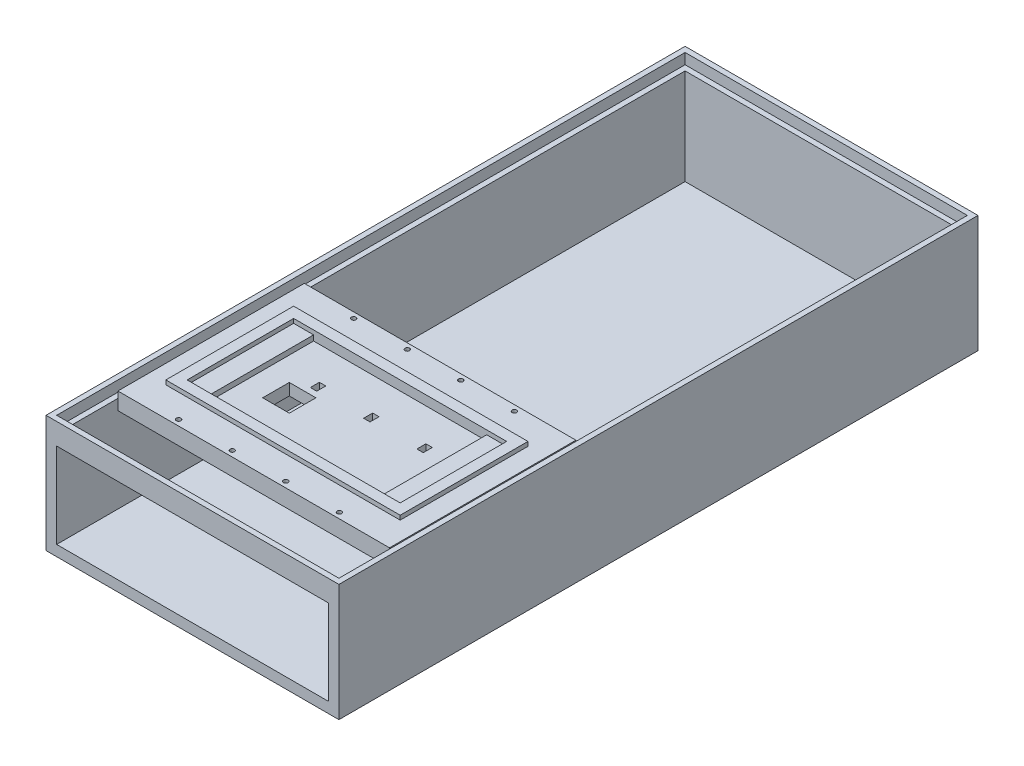
SolidWorks part; units mm, degrees
ref_plane "Front Plane" through (0, 0, 0) normal (0, 0, 1) x (1, 0, 0)
ref_plane "Top Plane" through (0, 0, 0) normal (0, 1, 0) x (1, 0, 0)
ref_plane "Right Plane" through (0, 0, 0) normal (1, 0, 0) x (0, 0, -1)
sketch "Sketch1" plane through (0, 0, 0) normal (0, 1, 0) x (1, 0, 0)
  line L1 (0, 0) -> (139.7, 0)
  line L2 (0, 0) -> (0, 304.8)
  line L3 (0, 304.8) -> (139.7, 304.8)
  line L4 (139.7, 0) -> (139.7, 304.8)
  dimension "D1" = 304.8
  dimension "D2" = 139.7
extrude "Boss-Extrude1" add sketch "Sketch1" along normal blind 5.08
sketch "Sketch2" plane through (0, 5.08, 0) normal (0, 1, 0) x (1, 0, 0)
  line L1 (0, 304.8) -> (139.7, 304.8)
  line L2 (0, 304.8) -> (0, 0)
  line L3 (0, 0) -> (139.7, 0)
  line L4 (139.7, 304.8) -> (139.7, 0)
  line L5 (5.08, 299.72) -> (134.62, 299.72)
  line L6 (5.08, 299.72) -> (5.08, 5.08)
  line L7 (5.08, 5.08) -> (134.62, 5.08)
  line L8 (134.62, 299.72) -> (134.62, 5.08)
  line M9 (0, 304.8) -> (0, 0)
  line M10 (0, 0) -> (139.7, 0)
  line M11 (139.7, 0) -> (139.7, 304.8)
  line M12 (139.7, 304.8) -> (0, 304.8)
  dimension "D1" = 5.08
  dimension "D2" = 5.08
  dimension "D3" = 5.08
  dimension "D4" = 5.08
extrude "Walls" add sketch "Sketch2" along normal blind 50.8 contours L5 L8 L7 L6 M12 M9 M10 M11 region at (69.85, 5.08, -301.4471)
sketch "Sketch3" plane through (0, 55.88, 0) normal (0, 1, 0) x (1, 0, 0)
  line L1 (5.08, 299.72) -> (134.62, 299.72)
  line L2 (5.08, 299.72) -> (5.08, 5.08)
  line L3 (5.08, 5.08) -> (134.62, 5.08)
  line L4 (134.62, 299.72) -> (134.62, 5.08)
  line L5 (2.54, 302.26) -> (137.16, 302.26)
  line L6 (2.54, 302.26) -> (2.54, 2.54)
  line L7 (2.54, 2.54) -> (137.16, 2.54)
  line L8 (137.16, 302.26) -> (137.16, 2.54)
  line M13 (5.08, 299.72) -> (134.62, 299.72)
  line M14 (134.62, 299.72) -> (134.62, 5.08)
  line M15 (134.62, 5.08) -> (5.08, 5.08)
  line M16 (5.08, 5.08) -> (5.08, 299.72)
  dimension "D1" = 2.54
  dimension "D2" = 2.54
  dimension "D3" = 2.54
  dimension "D4" = 2.54
extrude "Cut-Extrude1" cut sketch "Sketch3" against normal blind 5.08 contours L8 L5 L6 L7 M16 M13 M14 M15 region at (69.85, 55.88, -301.9314)
sketch "Sketch5" plane through (0, 5.08, 0) normal (0, 1, 0) x (1, 0, 0)
  line L0 (5.08, 5.08) -> (5.08, 299.72) construction
  line L1 (5.08, 118.11) -> (134.62, 118.11)
  line L2 (5.08, 118.11) -> (5.08, 29.21)
  line L3 (5.08, 29.21) -> (134.62, 29.21)
  line L4 (134.62, 118.11) -> (134.62, 29.21)
  line L6 (134.62, 299.72) -> (134.62, 5.08) construction
  point P8 (134.62, 73.66)
  dimension "D1" = 73.66
  dimension "D2" = 88.9
extrude "Button Support" add sketch "Sketch5" along normal blind 48.768
ref_plane "Plane1" through (0, 0, -73.66) normal (0, 0, 1) x (1, 0, 0)
sketch "Sketch6" plane through (0, 53.848, 0) normal (0, 1, 0) x (1, 0, 0)
  line L0 (0, 0) -> (139.7, 0) construction
  line L1 (19.05, 99.06) -> (120.65, 99.06)
  line L2 (19.05, 99.06) -> (19.05, 48.26)
  line L3 (19.05, 48.26) -> (120.65, 48.26)
  line L4 (120.65, 99.06) -> (120.65, 48.26)
  line L5 (125.73, 104.14) -> (13.97, 104.14)
  line L6 (125.73, 104.14) -> (125.73, 43.18)
  line L7 (125.73, 43.18) -> (13.97, 43.18)
  line L8 (13.97, 104.14) -> (13.97, 43.18)
  line L9 (134.62, 118.11) -> (5.08, 118.11) construction
  point P8 (69.85, 104.14)
  point P9 (69.85, 99.06)
  point P10 (120.65, 73.66)
  point P11 (125.73, 73.66)
  point P16 (69.85, 118.11)
  dimension "D1" = 50.8
  dimension "D2" = 73.66
  dimension "D3" = 101.6
  dimension "D4" = 5.08
  dimension "D5" = 5.08
extrude "Boss-Extrude4" add sketch "Sketch6" along normal blind 2.032
sketch "Sketch7" plane through (0, 53.848, 0) normal (0, 1, 0) x (1, 0, 0)
  line L0 (19.05, 48.26) -> (120.65, 48.26) construction
  line L1 (28.575, 48.26) -> (111.125, 48.26)
  line L2 (28.575, 48.26) -> (28.575, 99.06)
  line L3 (28.575, 99.06) -> (111.125, 99.06)
  line L4 (111.125, 48.26) -> (111.125, 99.06)
  line L5 (120.65, 99.06) -> (19.05, 99.06) construction
  point P8 (69.85, 99.06)
  point P9 (69.85, 48.26)
  dimension "D1" = 82.55
  dimension "D2" = 50.8
extrude "Cut-Extrude2" cut sketch "Sketch7" against normal blind 2.54
sketch "Sketch4" plane through (0, 0, 0) normal (0, 0, 1) x (1, 0, 0)
  line L0 (0, 0) -> (139.7, 0) construction
  line L1 (5.08, 45.72) -> (134.62, 45.72)
  line L2 (5.08, 45.72) -> (5.08, 5.08)
  line L3 (5.08, 5.08) -> (134.62, 5.08)
  line L4 (134.62, 45.72) -> (134.62, 5.08)
  line L5 (0, 55.88) -> (0, 0) construction
  line L6 (139.7, 55.88) -> (139.7, 0) construction
  line L7 (0, 55.88) -> (139.7, 55.88) construction
  dimension "D1" = 5.08
  dimension "D2" = 5.08
  dimension "D3" = 5.08
  dimension "D4" = 10.16
extrude "Cut-Extrude3" cut sketch "Sketch4" against normal blind 139.7
sketch "Sketch8" plane through (0, 51.308, 0) normal (0, 1, 0) x (1, 0, 0)
  line L0 (120.65, 99.06) -> (19.05, 99.06) construction
  line L1 (72.39, 79.085) -> (75.438, 79.085)
  line L2 (72.39, 79.085) -> (72.39, 83.403)
  line L3 (72.39, 83.403) -> (75.438, 83.403)
  line L4 (75.438, 79.085) -> (75.438, 83.403)
  line L5 (120.65, 48.26) -> (120.65, 99.06) construction
  line L6 (97.79, 79.085) -> (97.79, 83.403)
  line L7 (97.79, 79.085) -> (100.838, 79.085)
  line L8 (100.838, 79.085) -> (100.838, 83.403)
  line L9 (97.79, 83.403) -> (100.838, 83.403)
  line L10 (46.99, 79.085) -> (46.99, 83.403)
  line L11 (46.99, 79.085) -> (50.038, 79.085)
  line L12 (50.038, 79.085) -> (50.038, 83.403)
  line L13 (46.99, 83.403) -> (50.038, 83.403)
  dimension "D1" = 15.657
  dimension "D2" = 45.212
  dimension "D3" = 3.048
  dimension "D4" = 4.318
  dimension "D5" = 2
  dimension "D6" = 2
extrude "Haptic Wire Holes" cut sketch "Sketch8" against normal up to surface (5.588 mm away) up to face at (69.85, 45.72, -73.66)
sketch "Sketch9" plane through (0, 51.308, 0) normal (0, 1, 0) x (1, 0, 0)
  line L1 (52.5713, 76.1581) -> (39.8713, 76.1581)
  line L2 (52.5713, 76.1581) -> (52.5713, 63.4581)
  line L3 (52.5713, 63.4581) -> (39.8713, 63.4581)
  line L4 (39.8713, 76.1581) -> (39.8713, 63.4581)
  point P6 (0, 0)
  point P7 (0, 0)
  dimension "D1" = 12.7
  dimension "D2" = 12.7
extrude "Force Sensor Hole" cut sketch "Sketch9" against normal up to surface (5.588 mm away) up to face at (48.514, 45.72, -81.244)
sketch "Sketch10" plane through (0, 53.848, 0) normal (0, 1, 0) x (1, 0, 0)
  line L0 (5.08, 29.21) -> (134.62, 29.21) construction
  line L1 (134.62, 118.11) -> (134.62, 29.21) construction
  line L2 (-4.4704, 73.66) -> (4.4704, 73.66) construction
  circle A0 centre (108.0186, 31.9295) radius 1.0795
  circle A4 centre (82.4261, 31.9295) radius 1.0795
  circle A5 centre (56.9186, 31.9295) radius 1.0795
  circle A6 centre (31.3261, 31.9295) radius 1.0795
  circle A7 centre (31.3261, 115.3905) radius 1.0795
  circle A8 centre (56.9186, 115.3905) radius 1.0795
  circle A9 centre (82.4261, 115.3905) radius 1.0795
  circle A10 centre (108.0186, 115.3905) radius 1.0795
  point P12 (0, 0)
  dimension "D1" = 2.159
  dimension "D2" = 2.7195
  dimension "D3" = 26.6014
  dimension "D5" = 25.5925
  dimension "D6" = 25.5075
  dimension "D4" = 25.5925
extrude "NeoPixel Holes" cut sketch "Sketch10" against normal up to surface (8.128 mm away) up to face at (46.2213, 45.72, -69.8081)
